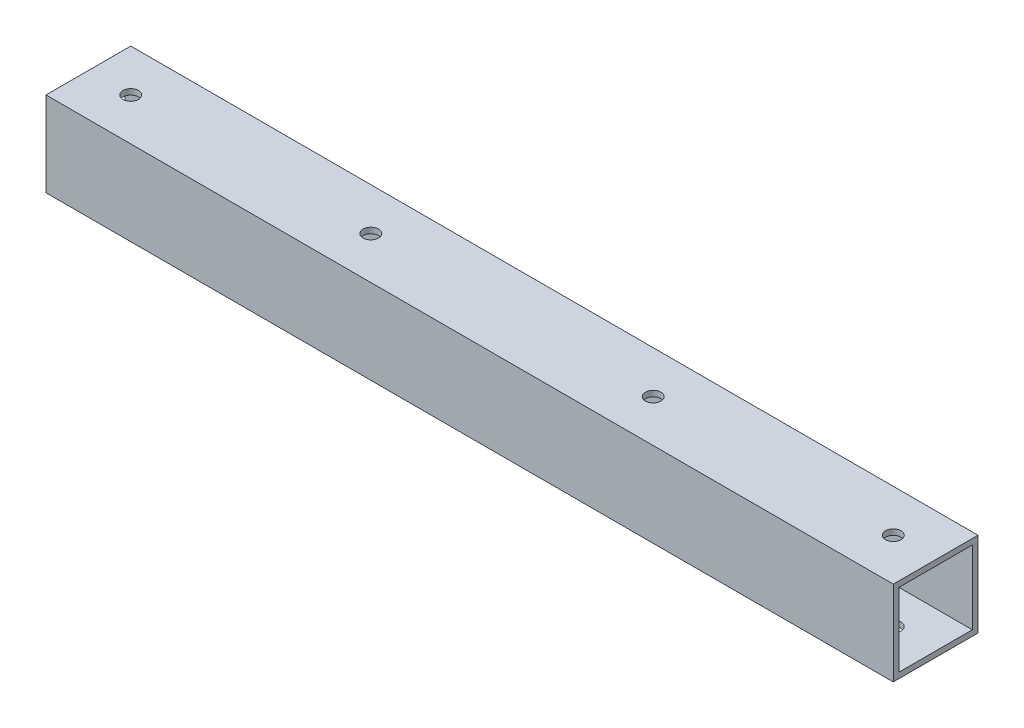
SolidWorks part; units mm, degrees
ref_plane "Front Plane" through (0, 0, 0) normal (0, 0, 1) x (1, 0, 0)
ref_plane "Top Plane" through (0, 0, 0) normal (0, 1, 0) x (1, 0, 0)
ref_plane "Right Plane" through (0, 0, 0) normal (1, 0, 0) x (0, 0, -1)
sketch "Sketch1" plane through (0, 0, 0) normal (1, 0, 0) x (0, 0, -1)
  line L1 (15, 15) -> (-15, 15)
  line L2 (15, 15) -> (15, -15)
  line L3 (15, -15) -> (-15, -15)
  line L4 (-15, 15) -> (-15, -15)
  line L5 (15, 15) -> (-15, -15) construction
  line L6 (15, -15) -> (-15, 15) construction
  line L7 (-13, 13) -> (13, 13)
  line L8 (-13, 13) -> (-13, -13)
  line L9 (-13, -13) -> (13, -13)
  line L10 (13, 13) -> (13, -13)
  line L11 (-13, 13) -> (13, -13) construction
  line L12 (-13, -13) -> (13, 13) construction
  point P0 (0, 0)
  point P5 (0, 0)
  dimension "D1" = 30
  dimension "D2" = 30
  dimension "D3" = 2
extrude "Boss-Extrude1" add sketch "Sketch1" along normal mid plane 300
sketch "Sketch2" plane through (0, 0, 0) normal (0, 1, 0) x (1, 0, 0)
  line L0 (150, 15) -> (150, -15) construction
  circle A0 centre (135, 0) radius 2.75
  dimension "D1" = 5.5
  dimension "D2" = 15
extrude "Cut-Extrude1" cut sketch "Sketch2" against normal through all both and the other way through all
mirror "Mirror1" about plane through (0, 0, 0) normal (1, 0, 0) of "Cut-Extrude1"
sketch "Sketch3" plane through (0, 0, 0) normal (0, 1, 0) x (1, 0, 0)
  line L0 (0, 0) -> (50, 0) construction
  line L1 (0, -16.5) -> (0, 16.5) construction
  circle A0 centre (50, 0) radius 2.75
  circle A1 centre (-50, 0) radius 2.75
  dimension "D2" = 5.5
  dimension "D1" = 50
extrude "Cut-Extrude2" cut sketch "Sketch3" against normal through all both and the other way through all
equation "\"D2@Sketch1\"=\"w\""
equation "\"D1@Sketch1\"=\"w\""
equation "\"t\"= 2"
equation "\"w\"= 30"
equation "\"D3@Sketch1\"=\"t\""
equation "\"D2@Sketch2\"=\"w\"/2"
